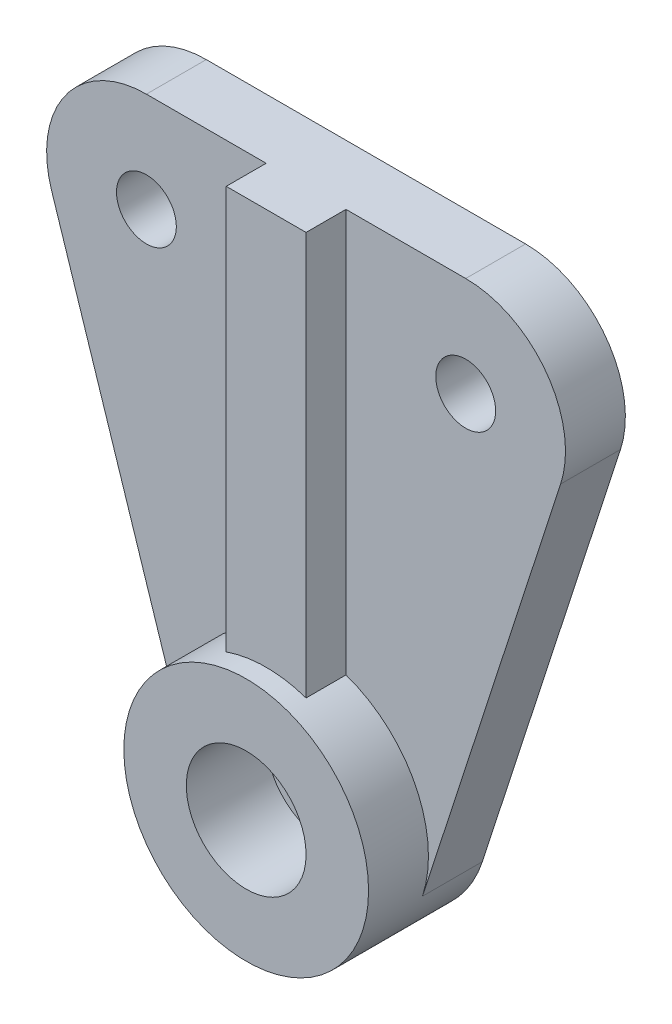
SolidWorks part; units mm, degrees
ref_plane "Płaszczyzna przednia" through (0, 0, 0) normal (0, 0, 1) x (1, 0, 0)
ref_plane "Płaszczyzna górna" through (0, 0, 0) normal (0, 1, 0) x (1, 0, 0)
ref_plane "Płaszczyzna prawa" through (0, 0, 0) normal (1, 0, 0) x (0, 0, -1)
sketch "Szkic1" plane through (0, 0, 0) normal (0, 0, 1) x (1, 0, 0)
  line L0 (0, 0) -> (0, 18.4141) construction
  line L1 (-8, 26) -> (8, 26)
  line L2 (-12.7561, 19.4576) -> (-5.8326, -1.8915)
  line L3 (5.8326, -1.8915) -> (12.7561, 19.4576)
  circle A0 centre (0, 0) radius 2.75
  circle A1 centre (8, 21) radius 1.5
  circle A2 centre (-8, 21) radius 1.5
  arc A3 (-8, 26) -> (-12.7561, 19.4576) centre (-8, 21) ccw
  arc A4 (12.7561, 19.4576) -> (8, 26) centre (8, 21) ccw
  arc A5 (-5.8326, -1.8915) -> (5.8326, -1.8915) centre (0, 0) ccw
  dimension "D1" = 3
  dimension "D2" = 5.5
  dimension "D5" = 8
  dimension "D3" = 8
  dimension "D4" = 21
extrude "Dodanie-wyciągnięcie1" add sketch "Szkic1" along normal blind 3
sketch "Szkic2" plane through (0, 0, 3) normal (0, 0, 1) x (1, 0, 0)
  circle A0 centre (0, 0) radius 2.75
  circle A1 centre (0, 0) radius 6.1316
  dimension "D1" = 5.5
extrude "Dodanie-wyciągnięcie2" add sketch "Szkic2" along normal blind 3
sketch "Szkic3" plane through (0, 0, 0) normal (0, 0, -1) x (-1, 0, 0)
  circle A0 centre (0, 0) radius 3
  circle A1 centre (0, 0) radius 1.6
extrude "Dodanie-wyciągnięcie3" add sketch "Szkic3" against normal blind 2
sketch "Szkic4" plane through (0, 0, 3) normal (0, 0, 1) x (1, 0, 0)
  line L0 (8, 26) -> (-8, 26) construction
  line L1 (-2, 5.3468) -> (2, 5.3468)
  line L2 (-2, 5.3468) -> (-2, 26)
  line L3 (-2, 26) -> (2, 26)
  line L4 (2, 5.3468) -> (2, 26)
  line L5 (-2, 5.3468) -> (2, 26) construction
  line L6 (-2, 26) -> (2, 5.3468) construction
  point P0 (0, 15.6734)
  dimension "D1" = 4
  dimension "D2" = 0
extrude "Dodanie-wyciągnięcie4" add sketch "Szkic4" along normal blind 2
sketch "Szkic5" plane through (0, 0, 0) normal (0, 0, -1) x (-1, 0, 0)
  line L0 (1.4081, 26) -> (18.7752, 26) construction
  line L1 (-8, 26) -> (8, 26) construction
  line L2 (0, -6.1316) -> (12.5879, -6.1316) construction
  arc A1 (-5.8326, -1.8915) -> (5.8326, -1.8915) centre (0, 0) ccw construction
  dimension "D1" = 32.1316
sketch "Szkic6" plane through (0, 0, 6) normal (0, 0, 1) x (1, 0, 0)
  circle A0 centre (0, 0) radius 3
  dimension "D1" = 6
extrude "Wytnij-wyciągnięcie1" cut sketch "Szkic6" against normal up to surface (4 mm away) up to face at (-1.6, 0, 2)
